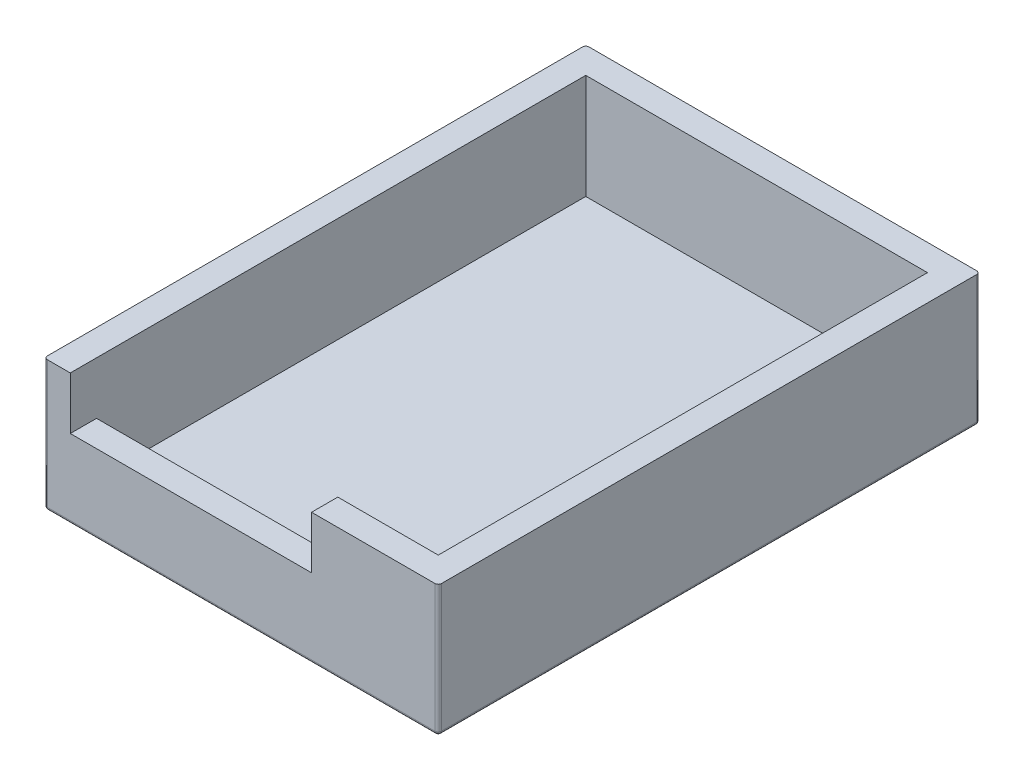
SolidWorks part; units mm, degrees
ref_plane "Front Plane" through (0, 0, 0) normal (0, 0, 1) x (1, 0, 0)
ref_plane "Top Plane" through (0, 0, 0) normal (0, 1, 0) x (1, 0, 0)
ref_plane "Right Plane" through (0, 0, 0) normal (1, 0, 0) x (0, 0, -1)
sketch "Sketch1" plane through (0, 0, 0) normal (0, 1, 0) x (1, 0, 0)
  line L1 (-15.03, -20.655) -> (15.03, -20.655)
  line L2 (-15.03, -20.655) -> (-15.03, 20.655)
  line L3 (-15.03, 20.655) -> (15.03, 20.655)
  line L4 (15.03, -20.655) -> (15.03, 20.655)
  line L5 (-15.03, -20.655) -> (15.03, 20.655) construction
  line L6 (-15.03, 20.655) -> (15.03, -20.655) construction
  point P0 (0, 0)
  dimension "D1" = 30.06
  dimension "D2" = 41.31
extrude "Boss-Extrude1" add sketch "Sketch1" along normal blind 10
shell "Shell2" thickness 2 removed face at (0, 10, 0)
sketch "Sketch4" plane through (0, 10, 0) normal (0, 1, 0) x (1, 0, 0)
  line L0 (-15.03, -20.655) -> (15.03, -20.655) construction
  line L1 (-13.03, -18.655) -> (5.37, -18.655)
  line L2 (-13.03, -18.655) -> (-13.03, -20.655)
  line L3 (-13.03, -20.655) -> (5.37, -20.655)
  line L4 (5.37, -18.655) -> (5.37, -20.655)
  dimension "D1" = 18.4
extrude "Cut-Extrude1" cut sketch "Sketch4" against normal blind 4
fillet "Fillet1" radius 0.25 8 edges at (0, 0, -20.655) (-15.03, 0, 0) (-15.03, 5, -20.655) (15.03, 5, -20.655) (-15.03, 5, 20.655) (15.03, 0, 0) (15.03, 5, 20.655) (0, 0, 20.655)
sketch "Sketch5" plane through (0, 0, 0) normal (0, -1, 0) x (1, 0, 0)
  circle A0 centre (3.9555, 14.6464) radius 1.5
  dimension "D1" = 3
extrude "Cut-Extrude2" cut sketch "Sketch5" against normal through all
sketch "Sketch6" plane through (0, 0, 0) normal (0, -1, 0) x (1, 0, 0)
  circle A0 centre (8.5786, 11.7254) radius 1.5
  dimension "D1" = 3
extrude "Cut-Extrude3" cut sketch "Sketch6" against normal through all
